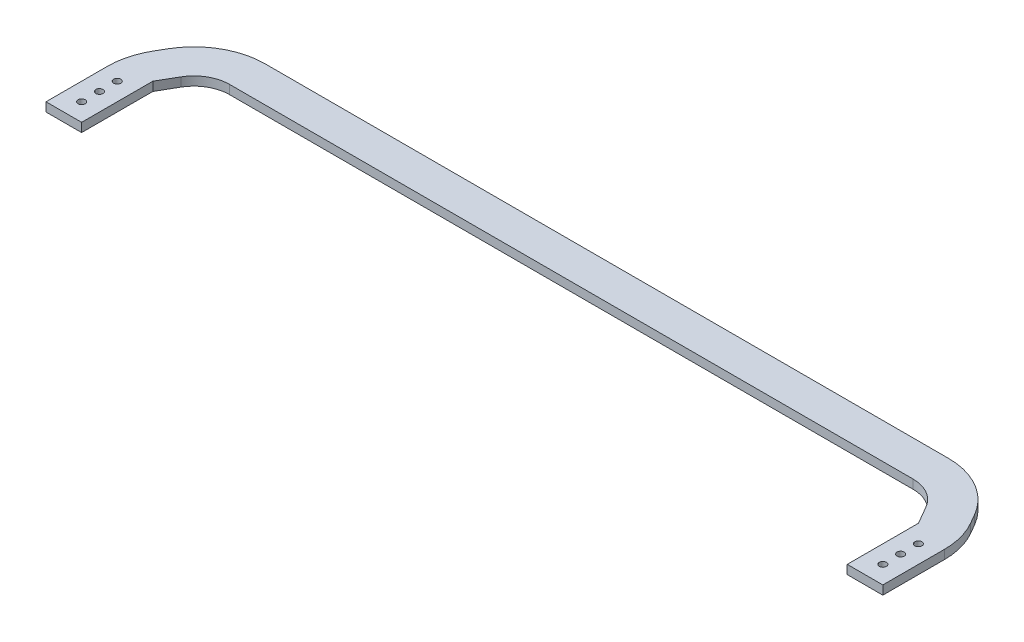
SolidWorks part; units mm, degrees
material "6061-T6 (SS)"
ref_plane "Front" through (0, 0, 0) normal (0, 0, 1) x (1, 0, 0)
ref_plane "Top" through (0, 0, 0) normal (0, 1, 0) x (1, 0, 0)
ref_plane "Right" through (0, 0, 0) normal (1, 0, 0) x (0, 0, -1)
sketch "Sketch1" plane through (0, 0, 0) normal (0, 1, 0) x (1, 0, 0)
  line L0 (-273.05, -50.8) -> (-273.05, 0)
  line L1 (273.05, 0) -> (273.05, -50.8)
  line L2 (273.05, -50.8) -> (298.45, -50.8)
  line L3 (0, 0) -> (0, -66.2098) construction
  line L4 (-273.05, -50.8) -> (-298.45, -50.8)
  line L5 (-298.45, -50.8) -> (-298.45, -6.8059)
  line L6 (298.45, -6.8059) -> (298.45, -50.8)
  line L7 (-273.05, 0) -> (-265.7177, 12.7)
  line L8 (-243.7206, 25.4) -> (243.7206, 25.4)
  line L9 (-273.05, 0) -> (273.05, 0) construction
  line L10 (265.7177, 12.7) -> (273.05, 0)
  line L11 (291.6441, 18.5941) -> (287.7147, 25.4)
  line L12 (243.7206, 50.8) -> (-243.7206, 50.8)
  line L13 (-287.7147, 25.4) -> (-291.6441, 18.5941)
  line L14 (298.45, 6.8059) -> (298.45, -50.8) construction
  line L15 (-298.45, -50.8) -> (-298.45, 6.8059) construction
  arc A6 (257.178, 9.9217) -> (273.05, 0) centre (252.5976, -15.0619) cw construction
  arc A7 (-298.45, 6.8059) -> (-273.9614, 41.9354) centre (-114.3541, -95.4263) cw construction
  arc A8 (-273.9614, 41.9354) -> (261.7583, 34.9053) centre (-26.8024, -1539.0619) cw construction
  arc A9 (261.7583, 34.9053) -> (298.45, 6.8059) centre (252.5976, -15.0619) cw construction
  arc A10 (-273.05, 0) -> (-260.4921, 18.3026) centre (-114.3541, -95.4263) cw construction
  arc A11 (-260.4921, 18.3026) -> (257.178, 9.9217) centre (-26.8024, -1539.0619) cw construction
  arc A12 (291.6441, 18.5941) -> (298.45, -6.8059) centre (247.65, -6.8059) cw
  arc A13 (287.7147, 25.4) -> (243.7206, 50.8) centre (243.7206, 0) ccw
  arc A14 (-298.45, -6.8059) -> (-291.6441, 18.5941) centre (-247.65, -6.8059) cw
  arc A15 (-243.7206, 50.8) -> (-287.7147, 25.4) centre (-243.7206, 0) ccw
  arc A16 (243.7206, 25.4) -> (265.7177, 12.7) centre (243.7206, 0) cw
  arc A17 (-265.7177, 12.7) -> (-243.7206, 25.4) centre (-243.7206, 0) cw
  dimension "D4" = 30
  dimension "D8" = 50.8
  dimension "D9" = 25.4
  dimension "D1" = 546.1
  dimension "D2" = 50.8
  dimension "D5" = 25.4
  dimension "D6" = 25.4
  dimension "D7" = 25.4
  dimension "D3" = 25.4
extrude "Boss-Extrude1" add sketch "Sketch1" along normal blind 6.35
hole_wizard "#10 Clearance Hole1" positions "Sketch2" profile "Sketch3" hole size "#10" standard "ANSI Inch" end condition through all
sketch "Sketch2" plane through (0, 6.35, 0) normal (0, 1, 0) x (1, 0, 0)
  line L3 (-298.45, -50.8) -> (-285.75, -38.1) construction
  line L4 (-285.75, -38.1) -> (-285.75, -25.4) construction
  line L5 (-285.75, -25.4) -> (-285.75, -12.7) construction
  line L6 (-285.75, -12.7) -> (-273.05, 0) construction
  line L8 (0, 0) -> (0, -50.8) construction
  point P0 (-285.75, -38.1)
  point P2 (-285.75, -25.4)
  point P4 (-285.75, -12.7)
  point P29 (285.75, -12.7)
  point P30 (285.75, -25.4)
  point P31 (285.75, -38.1)
  dimension "D1" = 12.7
sketch "Sketch3" plane through (-285.75, 6.35, 38.1) normal (1, 0, 0) x (0, 0, 1)
  line L0 (0, 0) -> (0, 6.35)
  line L1 (0, 6.35) -> (2.5527, 6.35)
  line L2 (2.5527, 6.35) -> (2.5527, 0)
  line L5 (2.5527, 0) -> (0, 0)
  line L11 (0, -6.35) -> (0, 107.95) construction
  dimension "Thru Hole Dia." = 5.1054
  dimension "Thru Hole Depth" = 6.35
